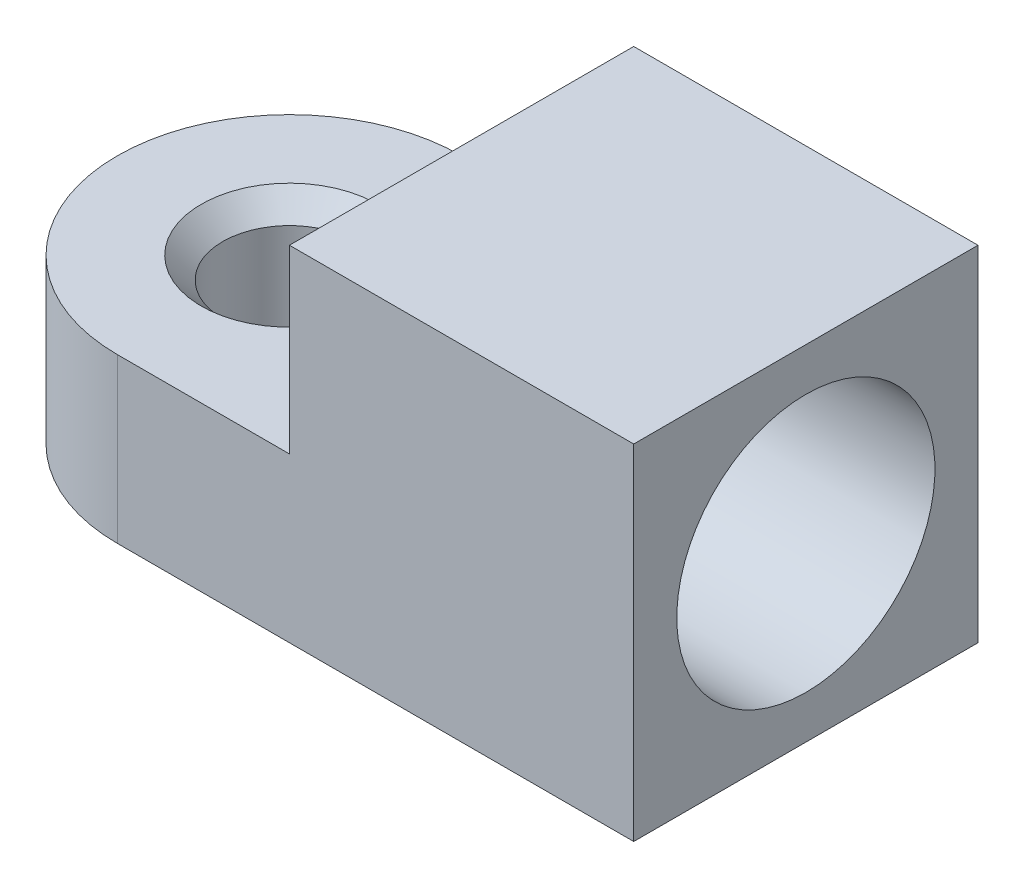
SolidWorks part; units mm, degrees
ref_plane "Ebene vorne" through (0, 0, 0) normal (0, 0, 1) x (1, 0, 0)
ref_plane "Ebene oben" through (0, 0, 0) normal (0, 1, 0) x (1, 0, 0)
ref_plane "Ebene rechts" through (0, 0, 0) normal (1, 0, 0) x (0, 0, -1)
sketch "Skizze1" plane through (0, 0, 0) normal (0, 0, 1) x (1, 0, 0)
  line L0 (-8, 0) -> (8, 0)
  line L1 (8, 0) -> (8, 8)
  line L2 (8, 8) -> (0, 8)
  line L3 (0, 8) -> (0, 3.8)
  line L4 (0, 3.8) -> (-8, 3.8)
  line L5 (-8, 3.8) -> (-8, 0)
  point P7 (0, 4.6795)
  dimension "D1" = 8
  dimension "D2" = 8
  dimension "D3" = 3.8
extrude "Aufsatz-Linear austragen1" add sketch "Skizze1" along normal mid plane 8
sketch "Skizze2" plane through (8, 0, 0) normal (1, 0, 0) x (0, 0, -1)
  line L0 (-4, 8) -> (4, 0) construction
  circle A0 centre (0, 4) radius 3
  dimension "D1" = 6
extrude "Schnitt-Linear austragen1" cut sketch "Skizze2" against normal blind 7
fillet "Verrundung1" radius 4 2 edges at (-8, 1.9, -4) (-8, 1.9, 4)
sketch "Skizze3" plane through (0, 3.8, 0) normal (0, 1, 0) x (1, 0, 0)
  circle A0 centre (-4, 0) radius 1.55
  arc A1 (-4, 4) -> (-8, 0) centre (-4, 0) ccw construction
  dimension "D1" = 3.1
extrude "Schnitt-Linear austragen2" cut sketch "Skizze3" against normal through all
chamfer "Fase1" distance 0.5 angle 45 1 edges at (-5.55, 3.8, 0)
